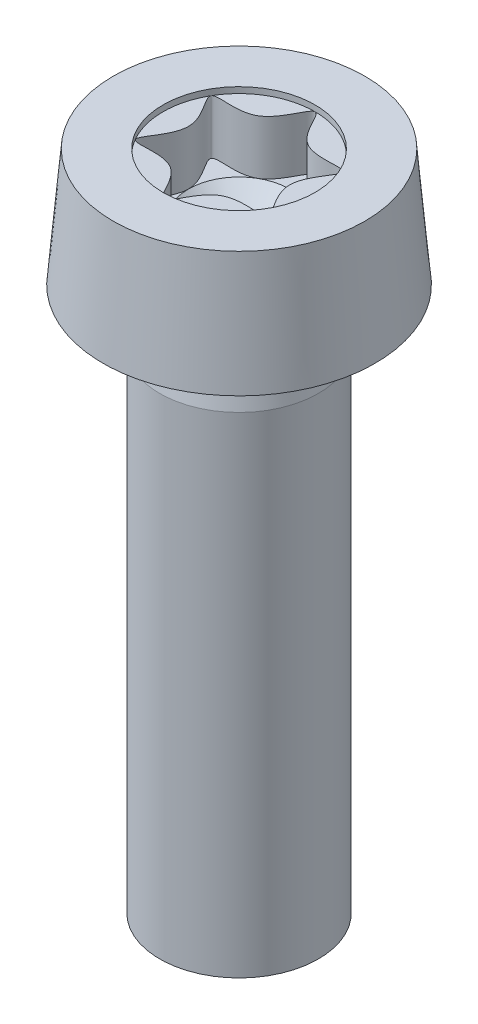
SolidWorks part; units mm, degrees
ref_plane "Front" through (0, 0, 0) normal (0, 0, 1) x (1, 0, 0)
ref_plane "Top" through (0, 0, 0) normal (0, 1, 0) x (1, 0, 0)
ref_plane "Right" through (0, 0, 0) normal (1, 0, 0) x (0, 0, -1)
sketch "Sketch1" plane through (0, 0, 0) normal (0, 0, 1) x (1, 0, 0)
  line L0 (0, 0) -> (0, 5.1006) construction
  line L1 (0, 14.6) -> (2.7725, 14.6)
  line L2 (2.7725, 14.6) -> (3, 12)
  line L3 (3, 12) -> (1.75, 12)
  line L4 (1.75, 0) -> (1.75, 10.8)
  line L5 (1.75, 0) -> (0, 0)
  line L6 (0, 0) -> (0, 14.6)
  line L7 (3, 12) -> (3, 11.4) construction
  line L8 (1.75, 10.8) -> (1.51, 12)
  line L9 (1.51, 12) -> (1.75, 12)
  line L10 (3, 11.4) -> (3, 0.6) construction
  dimension "D1" = 5
  dimension "thread_gap" = 1.2
  dimension "D2" = 0.24
revolve "Body-Revolve" add sketch "Sketch1" angle 360 about L0
cosmetic thread "ThreadCosmetic" [suppressed] parameters "D1"=33.8, "D2"=2.8505
fillet "Fillet1" radius 0.1 1 edges at (0, 12, -1.51)
sketch "Sketch2" plane through (0, 14.6, 0) normal (0, 1, 0) x (-1, 0, 0)
  line L0 (0, -1.8425) -> (0, 0)
  line L1 (0, 0) -> (-0.8375, -1.4506)
  circle A0 centre (0, 0) radius 1.675
  circle A1 centre (0, 0) radius 1.1167
  spline S0 degree 3 poles (0.3613, -0.6257) (0, -2.1996) (-0.3613, -0.6257) (-1.9049, -1.0998) (-0.7225, 0) (-1.9049, 1.0998) (-0.3613, 0.6257) (0, 2.1996) (0.3613, 0.6257) (1.9049, 1.0998) (0.7225, 0) (1.9049, -1.0998) (0.3613, -0.6257) (0, -2.1996) (-0.3613, -0.6257) knots -0.25 -0.166667 -0.083333 0 0.083333 0.166667 0.25 0.333333 0.416667 0.5 0.583333 0.666667 0.75 0.833333 0.916667 1 1.083333 1.166667 1.25 only from (0, -1.675) to (0, -1.675)
  point P5 (0, -1.675)
  point P7 (-0.5583, -0.9671)
  point P10 (-1.4506, -0.8375)
  point P11 (-1.4506, 0.8375)
  point P12 (0, 1.675)
  point P13 (1.4506, 0.8375)
  point P14 (1.4506, -0.8375)
  point P15 (-1.1167, 0)
  point P16 (-0.5583, 0.9671)
  point P17 (0.5583, 0.9671)
  point P18 (1.1167, 0)
  point P19 (0.5583, -0.9671)
  dimension "D1" = 2.2333
  dimension "D2" = 1.8425
  dimension "D3" = 30
extrude "Socket-Cut-Extrude1" cut sketch "Sketch2" against normal blind 1.33 contours S0
sketch "Sketch3" plane through (0, 14.6, 0) normal (0, 1, 0) x (-1, 0, 0)
  circle A0 centre (0, 0) radius 1.675
  dimension "D1" = 3.35
extrude "Socket-Cut-Extrude2" cut sketch "Sketch3" against normal blind 0.133
sketch "Sketch4" plane through (0, 0, 0) normal (0, 0, 1) x (1, 0, 0)
  line L0 (0, 13.27) -> (1.1167, 13.27)
  line L1 (1.4569, 13.27) -> (-1.4569, 13.27) construction
  line L2 (1.1167, 13.27) -> (0, 12.26)
  line L3 (0, 0) -> (0, 5.1006) construction
  line L4 (0, 12.26) -> (0, 13.27)
  line L5 (1.675, 14.6) -> (-1.675, 14.6) construction
  dimension "D1" = 2.34
  dimension "D2" = 1.1167
revolve "Drill-Cut-Revolve" cut sketch "Sketch4" angle 360 about axis through (0, 0, 0) along (0, 1, 0)
sketch "Sketch5" plane through (0, 0, 0) normal (0, 0, 1) x (1, 0, 0)
  line L0 (1.75, 0) -> (1.4252, 0.1875)
  line L1 (1.4252, 0.1875) -> (1.75, 0.375)
  line L2 (1.75, 0) -> (1.75, 10.8) construction
  line L3 (1.75, 0.375) -> (1.75, 0)
  line L4 (0, 0) -> (0, 5.1006) construction
  dimension "D1" = 1.4252
revolve "ThreadSchematic" [suppressed] cut sketch "Sketch5" angle 360 about axis through (0, 0, 0) along (0, 1, 0)
pattern_linear "ThdSchPat" [suppressed] count 56 spacing 0.6 along (0, 1, 0) of bodies 105
equation "\"D2@Sketch1\" = 0.2*\"thread_gap@Sketch1\""
equation "\"D1@Sketch2\" = \"socket_dia@Sketch2\" / 1.5"
equation "\"D2@Sketch2\" = \"socket_dia@Sketch2\" / 2 * 1.1"
equation "\"D1@Sketch3\" =\"socket_dia@Sketch2\""
equation "\"D1@Socket-Cut-Extrude2\" = .1 * \"socket_dep@Socket-Cut-Extrude1\""
equation "\"D1@Sketch4\" = 0.9*\"head_ht@Sketch1\""
equation "\"D2@Sketch4\" = \"D1@Sketch2\" / 2"
equation "\"D1@ThreadCosmetic\" = \"thread_length@Sketch1\""
equation "\"D2@ThreadCosmetic\" = \"dia@Sketch1\" - 1.0825 * \"pitch@Sketch1\""
equation "\"D1@Sketch5\" = \"D2@ThreadCosmetic\" / 2"
equation "\"D3@ThdSchPat\" = \"pitch@Sketch1\""
equation "\"D1@ThdSchPat\" = \"thread_length@Sketch1\" / \"pitch@Sketch1\""
